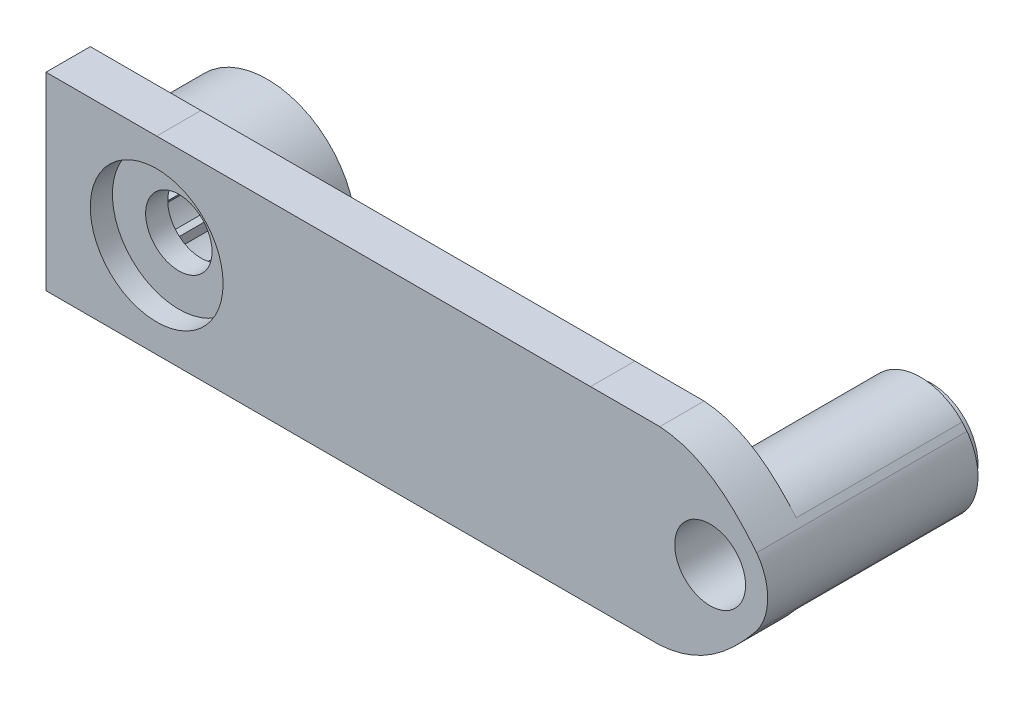
SolidWorks part; units mm, degrees
note: The reader was unsure of these and kept them because the rebuilt part matched: shared geometry of "Esboço1<4>", "Esboço1<5>", "Esboço1<10>", "Esboço1<12>".
ref_plane "Plano frontal" through (0, 0, 0) normal (0, 0, 1) x (1, 0, 0)
ref_plane "Plano superior" through (0, 0, 0) normal (0, 1, 0) x (1, 0, 0)
ref_plane "Plano direito" through (0, 0, 0) normal (1, 0, 0) x (0, 0, -1)
sketch "Esboço1" plane through (0, 0, 0) normal (0, 0, 1) x (1, 0, 0)
  line L0 (2.5, -9.4983) -> (2.5, -0.95)
  line L1 (-19.5, -9.4983) -> (-19.5, -0.9483)
  line L2 (-19.5, -9.4983) -> (0.1, -9.4983)
  line L3 (0.1, -9.4983) -> (0.1, -0.95) construction
  line L4 (-19.5, -0.9483) -> (0.1, -0.95)
  line L5 (-19.5, -0.9483) -> (-24.5, -0.9483)
  line L6 (-19.5, -0.9483) -> (-19.5, -9.4983)
  line L7 (-19.5, -9.4983) -> (-24.5, -9.4983)
  line L8 (-24.5, -0.9483) -> (-24.5, -9.4983)
  line L9 (0.1, -9.4983) -> (2.5, -9.4983)
  line L10 (0.1, -9.4983) -> (0.1, -0.95)
  line L11 (0.1, -0.95) -> (2.5, -0.95)
  line L13 (-12.9, -9.4983) -> (0.1, -9.4983) construction
  line L14 (-12.9, -9.4983) -> (-12.9, -0.95) construction
  line L15 (-12.9, -0.95) -> (0.1, -0.95) construction
  line L16 (0.1, -9.4983) -> (0.1, -0.95) construction
  line L17 (2.5, -9.4983) -> (3.2019, -9.4983)
  line L18 (2.5, -0.95) -> (3.2273, -0.95)
  line L22 (2.5, -2.225) -> (2.5, -8.225)
  line L23 (5.5, -5.2233) -> (7.1, -5.2233) construction
  circle A2 centre (-19.5, -5.2233) radius 1.5
  circle A3 centre (-19.5, -5.2233) radius 3
  circle A4 centre (5.5, -5.2233) radius 1.6
  circle A5 centre (-19.5, -5.2233) radius 4
  circle A6 centre (5.5, -5.2233) radius 2.6
  circle A7 centre (5.5, -5.2233) radius 2.1
  spline S0 degree 3 poles (2.5, -0.95) (4.7702, -0.797) (6.2763, -2.0641) (7.6033, -3.6948) knots 0 0 0 0 1 1 1 1
  spline S1 degree 3 poles (2.5, -9.4966) (4.7702, -9.6496) (6.2763, -8.3825) (7.6033, -6.7518) knots 0 0 0 0 1 1 1 1
  point P0 (0, 0)
  dimension "D3" = 3
  dimension "D4" = 6
  dimension "D6" = 3.2
  dimension "D14" = 8
  dimension "D1" = 8.55
  dimension "D2" = 19.6
  dimension "D5" = 5
  dimension "D8" = 25
  dimension "D9" = 13
  dimension "D10" = 3
  dimension "D11" = 1
  dimension "D12" = 0.5
extrude "Ressalto-extrusão1" add sketch "Esboço1" along normal blind 2
extrude "Ressalto-extrusão2" add sketch "Esboço1<4>" along normal blind 1
sketch "Esboço1<4>" plane through (0, 0, 0) normal (0, 0, 1) x (1, 0, 0) same geometry as "Esboço1"
extrude "Ressalto-extrusão3" add sketch "Esboço1<5>" against normal blind 7.5 contours A6 A4 | A7 A4
sketch "Esboço1<5>" plane through (0, 0, 0) normal (0, 0, 1) x (1, 0, 0) same geometry as "Esboço1"
extrude "Ressalto-extrusão18" add sketch "Esboço1<10>" against normal blind 3 contours L6 A5 A3 | L6 A5 A3
sketch "Esboço1<10>" plane through (0, 0, 0) normal (0, 0, 1) x (1, 0, 0) same geometry as "Esboço1"
sketch "Esboço4" plane through (0, 0, -3) normal (0, 0, -1) x (-1, 0, 0)
  line L0 (19.5, -5.2233) -> (17.0072, -3.5541) construction
  line L1 (18.3073, -3.0279) -> (18.3217, -2.4661)
  line L2 (17.4228, -3.8321) -> (17.1745, -3.328)
  line L4 (16.8618, -3.7951) -> (17.4228, -3.8321)
  line L5 (16.8901, -3.2795) -> (16.7457, -3.4955) [skipped]
  line L6 (17.8277, -2.7344) -> (18.3073, -3.0279)
  line L7 (19.4641, -2.7268) -> (19.7379, -2.236)
  line L8 (19.1759, -2.244) -> (19.4641, -2.7268)
  line L9 (20.6284, -2.9978) -> (21.0989, -2.6905)
  line L10 (20.5976, -2.4364) -> (20.6284, -2.9978)
  line L11 (21.5334, -3.7788) -> (22.0928, -3.7254)
  line L12 (21.767, -3.2674) -> (21.5334, -3.7788)
  line L13 (21.9718, -4.891) -> (22.4919, -5.1036)
  line L14 (22.4163, -4.5466) -> (21.9718, -4.891)
  line L15 (21.8431, -6.0795) -> (22.2048, -6.5095)
  line L16 (22.3967, -5.9811) -> (21.8431, -6.0795)
  line L17 (21.1768, -7.072) -> (21.2973, -7.6209)
  line L18 (21.7127, -7.2422) -> (21.1768, -7.072)
  line L19 (20.1256, -7.6412) -> (19.9772, -8.1832)
  line L20 (20.521, -8.041) -> (20.1256, -7.6412)
  line L21 (18.9303, -7.6567) -> (18.547, -8.0676)
  line L22 (19.0946, -8.1944) -> (18.9303, -7.6567)
  line L23 (17.8647, -7.1149) -> (17.3343, -7.3007)
  line L24 (17.7603, -7.6674) -> (17.8647, -7.1149)
  line L25 (17.1729, -6.14) -> (16.617, -6.058)
  line L26 (16.8237, -6.5807) -> (17.1729, -6.14)
  line L27 (17.0134, -4.9552) -> (16.5593, -4.6243)
  line L28 (16.4994, -5.1832) -> (17.0134, -4.9552)
  circle A0 centre (19.5, -5.2233) radius 3 construction
  circle A1 centre (19.5, -5.2233) radius 3
  point P7 (0, 0)
  point P8 (0, 0)
  circle M2 centre (19.5, -5.2233) radius 3
  dimension "D1" = 0.5
  dimension "D2" = 13
extrude "Ressalto-extrusão21" add sketch "Esboço1<12>" against normal blind 8 contours A7 A4
sketch "Esboço1<12>" plane through (0, 0, 0) normal (0, 0, 1) x (1, 0, 0) same geometry as "Esboço1"
extrude "Ressalto-extrusão22" add sketch "Esboço4" against normal blind 3 contours L4 L0 M2 | L0 L4 L2 A1
pattern_circular "PadrãoCircular4" count 13 over 360 about axis through (-19.5, -5.2233, 0) along (0, 0, 1) of "Ressalto-extrusão22"
